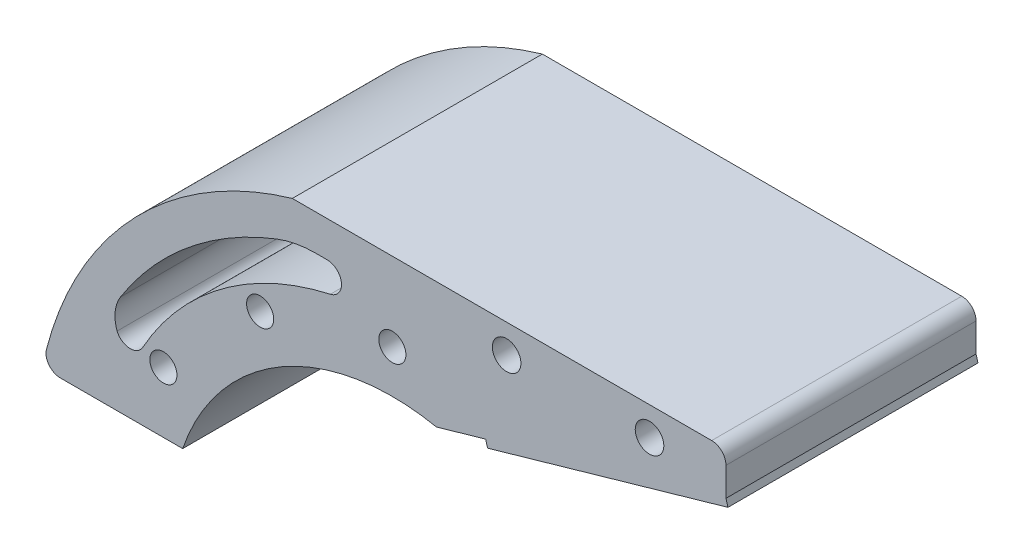
SolidWorks part; units mm, degrees
material "PBT 一般用途"
ref_plane "前视基准面" through (0, 0, 0) normal (0, 0, 1) x (1, 0, 0)
ref_plane "上视基准面" through (0, 0, 0) normal (0, 1, 0) x (1, 0, 0)
ref_plane "右视基准面" through (0, 0, 0) normal (1, 0, 0) x (0, 0, -1)
sketch "草图1" plane through (0, 0, 0) normal (0, 0, 1) x (1, 0, 0)
  line L0 (-54, 0) -> (54, 0) construction
  line L1 (0, 0) -> (0, 10) construction
  line L2 (-46.42, 26.4347) -> (-100.7026, 42)
  line L3 (46.42, 26.4347) -> (100.7026, 42)
  line L4 (-28.3826, 10) -> (28.3826, 10)
  line L5 (-100.7026, 42) -> (-100.7026, 48)
  line L6 (-100.7026, 48) -> (100.7026, 48)
  line L7 (100.7026, 48) -> (100.7026, 42)
  line L8 (-90, 44) -> (-70, 44) construction
  line L9 (90, 44) -> (70, 44) construction
  circle A0 centre (-54, 0) radius 26.5 construction
  circle A1 centre (54, 0) radius 26.5 construction
  arc A2 (-28.3826, 10) -> (-46.42, 26.4347) centre (-54, 0) ccw
  arc A3 (28.3826, 10) -> (46.42, 26.4347) centre (54, 0) cw
  circle A4 centre (-54, 0) radius 37 construction
  circle A5 centre (-54, 37) radius 1.9
  circle A6 centre (-35.5, 32.0429) radius 1.9
  circle A7 centre (-21.9571, 18.5) radius 1.9
  circle A8 centre (-17, 0) radius 1.9 construction
  circle A9 centre (17, 0) radius 1.9 construction
  circle A10 centre (21.9571, 18.5) radius 1.9
  circle A11 centre (35.5, 32.0429) radius 1.9
  circle A12 centre (54, 37) radius 1.9
  circle A13 centre (54, 0) radius 37 construction
  circle A14 centre (-90, 44) radius 2
  circle A15 centre (-70, 44) radius 2
  circle A16 centre (70, 44) radius 2
  circle A17 centre (90, 44) radius 2
  point P2 (0, 0)
  dimension "D2" = 53
  dimension "D3" = 55
  dimension "D8" = 74
  dimension "D9" = 3.8
  dimension "D11" = 20
  dimension "D13" = 4
  dimension "D1" = 108
  dimension "D4" = 16
  dimension "D5" = 10
  dimension "D6" = 6
  dimension "D7" = 38
  dimension "D12" = 70
  dimension "D14" = 4
  dimension "D10" = 4
extrude "凸台-拉伸1" add sketch "草图1" along normal blind 35
sketch "草图2" plane through (0, 0, 35) normal (0, 0, 1) x (1, 0, 0)
  line L0 (-100.7026, 42) -> (-100.9783, 41.0387)
  line L1 (-100.9783, 41.0387) -> (-67.3341, 31.3914)
  line L2 (-67.3341, 31.3914) -> (-67.0585, 32.3527)
  line L3 (-100.7026, 42) -> (-46.42, 26.4347) construction
  line L4 (-67.0585, 32.3527) -> (-100.7026, 42)
  line L5 (0, 10) -> (0, 48) construction
  line L6 (-28.3826, 10) -> (28.3826, 10) construction
  line L7 (100.7026, 48) -> (-100.7026, 48) construction
  line L8 (67.0585, 32.3527) -> (100.7026, 42)
  line L9 (67.3341, 31.3914) -> (67.0585, 32.3527)
  line L10 (100.9783, 41.0387) -> (67.3341, 31.3914)
  line L11 (100.7026, 42) -> (100.9783, 41.0387)
  dimension "D1" = 1
  dimension "D2" = 35
extrude "凸台-拉伸2" add sketch "草图2" against normal up to surface (35 mm away) up to face at (0, 32.1362, 0)
sketch "草图3" plane through (0, 0, 35) normal (0, 0, 1) x (1, 0, 0)
  line L1 (-6.6417, 40.2101) -> (-15.4766, 19.6585)
  line L3 (-10.8374, 17.7899) -> (-1.8374, 38.7258)
  line L4 (1.8374, 38.7258) -> (10.8374, 17.7899)
  line L5 (9, 15) -> (-9, 15)
  line L6 (-44.8896, 43) -> (-8.4792, 43)
  line L7 (100.7026, 48) -> (-100.7026, 48) construction
  line L8 (-28.3826, 10) -> (28.3826, 10) construction
  line L9 (0, 15) -> (0, 10) construction
  line L10 (44.8896, 43) -> (8.4792, 43)
  line L11 (6.6417, 40.2101) -> (15.4766, 19.6585)
  circle A0 centre (-54, 0) radius 40 construction
  arc A1 (-45.3234, 39.0476) -> (-19.0609, 19.4746) centre (-54, 0) cw
  arc A2 (-45.3234, 39.0476) -> (-44.8896, 43) centre (-44.8896, 41) cw
  arc A3 (10.8374, 17.7899) -> (9, 15) centre (9, 17) cw
  arc A4 (-10.8374, 17.7899) -> (-9, 15) centre (-9, 17) ccw
  arc A5 (-1.8374, 38.7258) -> (1.8374, 38.7258) centre (0, 37.9359) cw
  arc A6 (-8.4792, 43) -> (-6.6417, 40.2101) centre (-8.4792, 41) cw
  arc A7 (-19.0609, 19.4746) -> (-15.4766, 19.6585) centre (-17.314, 20.4484) ccw
  arc A8 (45.3234, 39.0476) -> (44.8896, 43) centre (44.8896, 41) ccw
  arc A9 (45.3234, 39.0476) -> (19.0609, 19.4746) centre (54, 0) ccw
  arc A10 (8.4792, 43) -> (6.6417, 40.2101) centre (8.4792, 41) ccw
  arc A11 (19.0609, 19.4746) -> (15.4766, 19.6585) centre (17.314, 20.4484) cw
  point P10 (0, 15)
  point P25 (0, 43)
  dimension "D1" = 80
  dimension "D2" = 5
  dimension "D4" = 2
  dimension "D6" = 2
  dimension "D3" = 5
  dimension "D5" = 5
  dimension "D7" = 18
extrude "切除-拉伸1" cut sketch "草图3" against normal through all
sketch "草图4" plane through (0, 0, 0) normal (0, 0, -1) x (-1, 0, 0)
  line L0 (0, 0) -> (0, 48) construction
  line L1 (-100.7026, 48) -> (100.7026, 48) construction
  circle A0 centre (54, 0) radius 41.5
  circle A1 centre (-54, 0) radius 41.5
  dimension "D1" = 83
extrude "切除-拉伸2" cut sketch "草图4" against normal blind 5.5
sketch "草图5" plane through (0, 0, 5.5) normal (0, 0, -1) x (-1, 0, 0)
  circle A0 centre (-54, 0) radius 31
  circle A1 centre (54, 0) radius 31
  dimension "D1" = 62
extrude "切除-拉伸3" cut sketch "草图5" against normal through all
sketch "草图6" plane through (0, 0, 0) normal (0, 0, -1) x (-1, 0, 0)
  line L0 (0, 0) -> (-54, 0) construction
  line L1 (-13.9839, 87.6552) -> (-42.2298, 48.5949)
  line L2 (-13.9839, 87.6552) -> (112.2367, 87.6552)
  line L3 (112.2367, 87.6552) -> (108.7339, 6.0131)
  line L4 (108.7339, 6.0131) -> (-4, 0)
  circle A0 centre (-54, 0) radius 50
  circle M3 centre (90, 44) radius 2
  circle M4 centre (70, 44) radius 2
  line M7 (-13.7228, 10) -> (13.7228, 10)
  arc M8 (13.7228, 10) -> (16.8528, 18.5023) centre (54, 0) cw
  arc M9 (16.8528, 18.5023) -> (15.4766, 19.6585) centre (17.314, 20.4484) cw
  line M10 (15.4766, 19.6585) -> (6.6417, 40.2101)
  arc M11 (6.6417, 40.2101) -> (8.4792, 43) centre (8.4792, 41) cw
  line M12 (8.4792, 43) -> (44.8896, 43)
  arc M13 (44.8896, 43) -> (46.8863, 40.8858) centre (44.8896, 41) cw
  arc M14 (46.8863, 40.8858) -> (77.3958, 34.2766) centre (54, 0) cw
  line M15 (77.3958, 34.2766) -> (100.9783, 41.0387)
  line M16 (100.9783, 41.0387) -> (100.7026, 42)
  line M17 (100.7026, 42) -> (100.7026, 48)
  line M18 (100.7026, 48) -> (-100.7026, 48)
  line M24 (-44.8896, 43) -> (-8.4792, 43)
  arc M25 (-8.4792, 43) -> (-6.6417, 40.2101) centre (-8.4792, 41) cw
  line M26 (-6.6417, 40.2101) -> (-15.4766, 19.6585)
  line M29 (9, 15) -> (-9, 15)
  line M31 (-10.8374, 17.7899) -> (-1.8374, 38.7258)
  arc M32 (-1.8374, 38.7258) -> (1.8374, 38.7258) centre (0, 37.9359) cw
  line M33 (1.8374, 38.7258) -> (10.8374, 17.7899)
  arc M34 (10.8374, 17.7899) -> (9, 15) centre (9, 17) cw
  dimension "D1" = 100
extrude "切除-拉伸4" cut sketch "草图6" against normal blind 90 contours A0 L4 L3 L2 L1 M18 M17 M16 M15 M14 M13 M12 M11 M10 M9 M8 M7 | A0 M7 M8 M9 M10 M11 M12 M13 M14 M15 M16 M17 M18 M24 M25 M26 M31 M32 M33 M34 M29 M3 M4 region at (-47.6595, 48.71, 0) region at (-30.3513, 46.5399, 0)
sketch "草图7" plane through (0, 0, 0) normal (0, 0, -1) x (-1, 0, 0)
  line L0 (0, 0) -> (-54, 0) construction
  line L1 (-40, 48) -> (-68, 48)
  line L2 (-100.7026, 48) -> (-40, 48) construction
  line L3 (-67.3341, 31.3914) -> (-100.9783, 41.0387)
  line L4 (-28.4853, 43) -> (-44.8896, 43)
  line L5 (-5.0102, 10) -> (-24.6572, 10)
  circle A0 centre (-54, 0) radius 40
  arc A1 (-19.0609, 19.4746) -> (-45.3234, 39.0476) centre (-54, 0) ccw construction
  circle A2 centre (-54, 0) radius 41.5
  arc A3 (-46.8863, 40.8858) -> (-77.3958, 34.2766) centre (-54, 0) ccw construction
  circle A4 centre (-54, 0) radius 50
  circle A5 centre (-54, 0) radius 45
  dimension "D1" = 5
extrude "凸台-拉伸3" add sketch "草图7" against normal up to surface (35 mm away) contours A5 L5 A4 L4 region at (18.3122, 28.5978, 0) up to face at (68, 44, 35)
fillet "圆角1" radius 15 1 edges at (40.7335, 43, 17.5)
fillet "圆角2" radius 5 1 edges at (14.5897, 21.7216, 17.5)
fillet "圆角3" radius 2 2 edges at (5.0102, 10, 17.5) (100.7026, 48, 17.5)
sketch "草图8" plane through (0, 0, 35) normal (0, 0, 1) x (1, 0, 0)
  line L4 (60.1748, 30.3788) -> (67.0585, 32.3527)
  line L5 (13.7228, 10) -> (24.6572, 10)
  line L6 (67.3341, 31.3914) -> (77.3958, 34.2766)
  line L7 (67.0585, 32.3527) -> (67.3341, 31.3914)
  line L8 (60.1748, 30.3788) -> (67.0585, 32.3527)
  line L9 (13.7228, 10) -> (24.6572, 10)
  line L10 (67.3341, 31.3914) -> (77.3958, 34.2766)
  line L11 (67.0585, 32.3527) -> (67.3341, 31.3914)
  arc A6 (60.1748, 30.3788) -> (24.6572, 10) centre (54, 0) ccw
  arc A7 (16.8528, 18.5023) -> (13.7228, 10) centre (54, 0) ccw
  arc A8 (16.8528, 18.5023) -> (19.0609, 19.4746) centre (17.314, 20.4484) ccw
  arc A9 (45.3234, 39.0476) -> (19.0609, 19.4746) centre (54, 0) ccw
  arc A10 (45.3234, 39.0476) -> (46.8863, 40.8858) centre (44.8896, 41) ccw
  arc A11 (77.3958, 34.2766) -> (46.8863, 40.8858) centre (54, 0) ccw
  arc A12 (60.1748, 30.3788) -> (24.6572, 10) centre (54, 0) ccw
  arc A13 (16.8528, 18.5023) -> (13.7228, 10) centre (54, 0) ccw
  arc A14 (16.8528, 18.5023) -> (19.0609, 19.4746) centre (17.314, 20.4484) ccw
  arc A15 (45.3234, 39.0476) -> (19.0609, 19.4746) centre (54, 0) ccw
  arc A16 (45.3234, 39.0476) -> (46.8863, 40.8858) centre (44.8896, 41) ccw
  arc A17 (77.3958, 34.2766) -> (46.8863, 40.8858) centre (54, 0) ccw
  dimension "D1" = 0
extrude "切除-拉伸5" cut sketch "草图8" against normal blind 5.5
sketch "草图10" plane through (0, 0, 29.5) normal (0, 0, 1) x (1, 0, 0)
  line L4 (67.0585, 32.3527) -> (67.3341, 31.3914)
  line L5 (67.3341, 31.3914) -> (77.3958, 34.2766)
  line L6 (13.7228, 10) -> (24.6572, 10)
  line L7 (60.1748, 30.3788) -> (67.0585, 32.3527)
  line L8 (67.0585, 32.3527) -> (67.3341, 31.3914)
  line L9 (67.3341, 31.3914) -> (77.3958, 34.2766)
  line L10 (13.7228, 10) -> (24.6572, 10)
  line L11 (60.1748, 30.3788) -> (67.0585, 32.3527)
  circle A0 centre (54, 37) radius 1.9 construction
  circle A1 centre (35.5, 32.0429) radius 1.9 construction
  circle A2 centre (21.9571, 18.5) radius 1.9 construction
  circle A3 centre (54, 37) radius 1.9
  circle A4 centre (35.5, 32.0429) radius 1.9
  circle A5 centre (21.9571, 18.5) radius 1.9
  arc A6 (77.3958, 34.2766) -> (46.8863, 40.8858) centre (54, 0) ccw
  arc A7 (45.3234, 39.0476) -> (46.8863, 40.8858) centre (44.8896, 41) ccw
  arc A8 (45.3234, 39.0476) -> (19.0609, 19.4746) centre (54, 0) ccw
  arc A9 (16.8528, 18.5023) -> (19.0609, 19.4746) centre (17.314, 20.4484) ccw
  arc A10 (16.8528, 18.5023) -> (13.7228, 10) centre (54, 0) ccw
  arc A11 (60.1748, 30.3788) -> (24.6572, 10) centre (54, 0) ccw
  arc A12 (77.3958, 34.2766) -> (46.8863, 40.8858) centre (54, 0) ccw
  arc A13 (45.3234, 39.0476) -> (46.8863, 40.8858) centre (44.8896, 41) ccw
  arc A14 (45.3234, 39.0476) -> (19.0609, 19.4746) centre (54, 0) ccw
  arc A15 (16.8528, 18.5023) -> (19.0609, 19.4746) centre (17.314, 20.4484) ccw
  arc A16 (16.8528, 18.5023) -> (13.7228, 10) centre (54, 0) ccw
  arc A17 (60.1748, 30.3788) -> (24.6572, 10) centre (54, 0) ccw
  dimension "D1" = 0
extrude "凸台-拉伸5" add sketch "草图10" along normal up to surface (5.5 mm away) up to face at (47.5176, 33.2988, 35)
